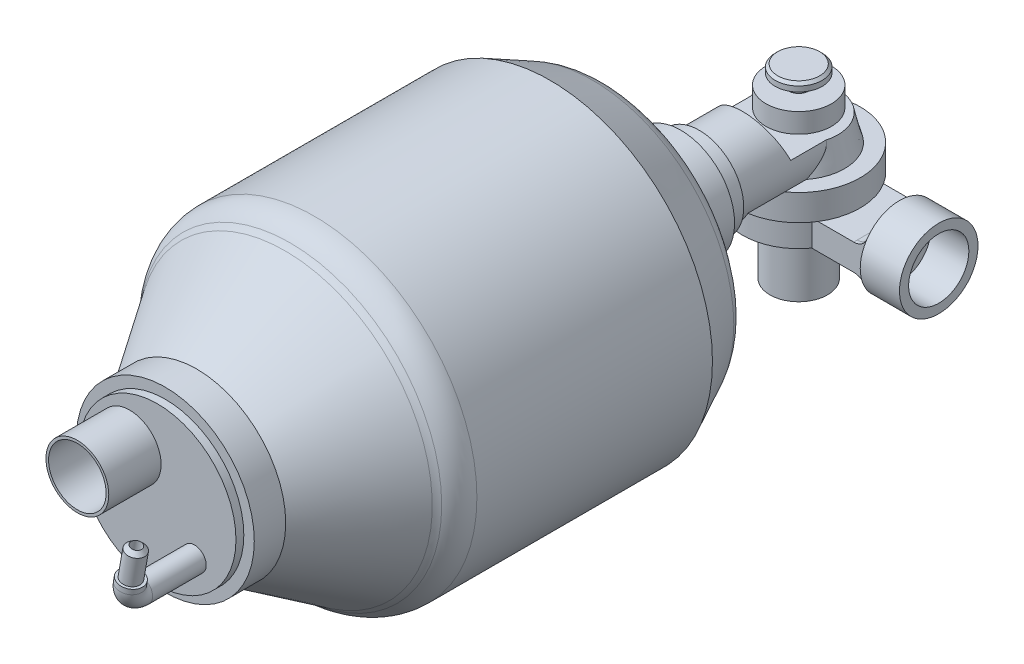
SolidWorks part; units mm, degrees
ref_plane "Front Plane" through (0, 0, 0) normal (0, 0, 1) x (1, 0, 0)
ref_plane "Top Plane" through (0, 0, 0) normal (0, 1, 0) x (1, 0, 0)
ref_plane "Right Plane" through (0, 0, 0) normal (1, 0, 0) x (0, 0, -1)
sketch "Sketch1" plane through (0, 0, 0) normal (1, 0, 0) x (0, 0, -1)
  line L5 (-92.5, 0) -> (92.5, 0)
  line L6 (92.5, 0) -> (92.5, 20.5)
  line L7 (-47.5, 62.05) -> (42.5, 62.05)
  line L8 (42.5, 62.05) -> (62.5, 52.05)
  line L9 (62.5, 52.05) -> (78.5, 20.5)
  line L10 (78.5, 20.5) -> (92.5, 20.5)
  line L11 (-47.5, 62.05) -> (-47.5, 57.05) construction
  line L12 (-47.5, 57.05) -> (-57.5, 57.05) construction
  line L13 (-92.5, 0) -> (-92.5, 34)
  line L14 (-92.5, 34) -> (-57.5, 57.05)
  arc A6 (-47.5, 62.05) -> (-57.5, 57.05) centre (-47.5, 49.55) ccw
  dimension "D4" = 50
  dimension "D11" = 5
  dimension "D1" = 185
  dimension "D2" = 20.5
  dimension "D3" = 90
  dimension "D5" = 20
  dimension "D6" = 10
  dimension "D7" = 62.05
  dimension "D8" = 14
  dimension "D9" = 10
  dimension "D10" = 34
revolve "Revolve1" add sketch "Sketch1" angle 360 about L5
fillet "Fillet1" radius 5 1 edges at (20.5, 0, -78.5)
fillet "Fillet2" radius 12.54 1 edges at (52.05, 0, -62.5)
fillet "Fillet5" radius 10 1 edges at (57.05, 0, 57.5)
sketch "Sketch2" plane through (0, 0, 92.5) normal (0, 0, 1) x (1, 0, 0)
  circle A0 centre (0, 0) radius 34
  circle A1 centre (0, 0) radius 34 construction
extrude "Boss-Extrude1" add sketch "Sketch2" along normal blind 12
sketch "Sketch3" plane through (0, 0, 104.5) normal (0, 0, 1) x (1, 0, 0)
  circle A0 centre (0, 0) radius 30
  dimension "D1" = 60
extrude "Boss-Extrude2" add sketch "Sketch3" along normal blind 3
sketch "Sketch4" plane through (0, 0, 107.5) normal (0, 0, 1) x (1, 0, 0)
  line L0 (-10.6066, 10.6066) -> (14.1421, -14.1421) construction
  line L1 (0, 0) -> (0, 16.2779) construction
  line L2 (14.1421, -14.1421) -> (16.6659, 0.1707) construction
  dimension "D4" = 55
  dimension "D1" = 45
  dimension "D2" = 15
  dimension "D3" = 20
sketch "Sketch5" plane through (0, 0, 107.5) normal (0, 0, 1) x (1, 0, 0)
  circle A0 centre (-10.6066, 10.6066) radius 12
  circle A1 centre (-10.6066, 10.6066) radius 11
  dimension "D1" = 24
  dimension "D2" = 22
extrude "Boss-Extrude3" add sketch "Sketch5" along normal blind 20
ref_plane "Plane2" through (16.1341, -2.8449, 0) normal (0.9848, -0.1736, 0) x (0.1736, 0.9848, 0)
sketch "Sketch10" plane through (16.1341, -2.8449, 0) normal (0.9848, -0.1736, 0) x (0.1736, 0.9848, 0)
  line L0 (-11.4715, 107.5) -> (-11.4715, 128)
  line L1 (-6.4715, 133) -> (-4.4715, 133)
  arc A0 (-11.4715, 128) -> (-6.4715, 133) centre (-6.4715, 128) cw
  dimension "D3" = 5
  dimension "D1" = 7
  dimension "D2" = 25.5
sketch "Sketch8" plane through (0, 0, 107.5) normal (0, 0, 1) x (1, 0, 0)
  circle A0 centre (14.1421, -14.1421) radius 4.5
  circle A2 centre (14.1421, -14.1421) radius 2.5
  dimension "D1" = 9
  dimension "D2" = 5
sweep "Sweep2" add profiles "Sketch8" path "Sketch10"
sketch "Sketch13" plane through (-0.7765, -4.4036, 0) normal (0.1736, 0.9848, 0) x (0.9848, -0.1736, 0)
  circle A0 centre (16.383, -133) radius 3.5
  circle A1 centre (16.383, -133) radius 2
  dimension "D1" = 7
  dimension "D2" = 4
extrude "Boss-Extrude5" add sketch "Sketch13" along normal blind 12
chamfer "Chamfer2" distance 1.5 angle 45 1 edges at (13.9946, 5.177, 133)
sketch "Sketch15" plane through (0, 0, -92.5) normal (0, 0, -1) x (-1, 0, 0)
  circle A0 centre (0, 0) radius 17
  dimension "D1" = 34
extrude "Boss-Extrude6" add sketch "Sketch15" along normal blind 7
sketch "Sketch16" plane through (0, 0, -99.5) normal (0, 0, -1) x (-1, 0, 0)
  circle A0 centre (0, 0) radius 15
  dimension "D1" = 30
extrude "Boss-Extrude7" add sketch "Sketch16" along normal blind 45 from surface starting at face at (-17, 0, -92.5)
ref_plane "Plane3" through (0, 4, 0) normal (0, 1, 0) x (1, 0, 0)
sketch "Sketch21" plane through (0, 0, -137.5) normal (0, 0, -1) x (-1, 0, 0)
  line L0 (0, 0) -> (0, 4) construction
  line L1 (0, 0) -> (0, -6) construction
  point P4 (0, 4)
  dimension "D1" = 4
  dimension "D2" = 6
sketch "Sketch24" plane through (0, 4, 0) normal (0, 1, 0) x (1, 0, 0)
  circle A0 centre (0, 137.5) radius 15
  dimension "D1" = 30
ref_plane "Plane4" through (0, -6, 0) normal (0, 1, 0) x (1, 0, 0)
sketch "Sketch25" plane through (0, -6, 0) normal (0, 1, 0) x (1, 0, 0)
  circle A0 centre (0, 137.5) radius 17.5
  dimension "D1" = 35
loft "Loft1" add profiles "Sketch25", "Sketch24" connector at (-3.5057, -6, -154.6453) connector at (-0.8854, 4, -152.4738)
sketch "Sketch26" plane through (0, 0, 0) normal (1, 0, 0) x (0, 0, -1)
  line L0 (137.5, 4) -> (120, 4)
  line L1 (68.255, 4) -> (-68.255, 4) construction
  line L2 (120, 4) -> (115.6324, 16)
  line L3 (115.6324, 16) -> (137.5, 16)
  line L4 (137.5, 16) -> (137.5, 4)
  line L5 (137.5, -6) -> (104.5, -6)
  line L6 (137.5, 0) -> (137.5, -6) construction
  line L7 (68.255, -6) -> (-68.255, -6) construction
  line L8 (104.5, -6) -> (100.8603, -16)
  line L9 (100.8603, -16) -> (137.5, -16)
  line L10 (137.5, -16) -> (137.5, -6)
  line L11 (99.5, -15) -> (99.5, 15) construction
  dimension "D1" = 17.5
  dimension "D2" = 70
  dimension "D3" = 12
  dimension "D4" = 70
  dimension "D5" = 5
  dimension "D6" = 10
extrude "Cut-Extrude1" cut sketch "Sketch26" against normal mid plane 40
sketch "Sketch27" plane through (0, -6, 0) normal (0, -1, 0) x (1, 0, 0)
  circle A0 centre (0, -137.5) radius 23.5
  dimension "D1" = 47
extrude "Boss-Extrude8" add sketch "Sketch27" along normal blind 10
sketch "Sketch28" plane through (0, -16, 0) normal (0, -1, 0) x (1, 0, 0)
  circle A0 centre (0, -137.5) radius 21.5
  dimension "D1" = 43
extrude "Boss-Extrude9" add sketch "Sketch28" along normal blind 10
sketch "Sketch29" plane through (0, 4, 0) normal (0, 1, 0) x (1, 0, 0)
  circle A0 centre (0, 137.5) radius 10
  dimension "D1" = 20
extrude "Boss-Extrude10" add sketch "Sketch29" along normal blind 9
ref_plane "Plane5" through (0, 5.5, 0) normal (0, 1, 0) x (1, 0, 0)
sketch "Sketch30" plane through (0, 5.5, 0) normal (0, 1, 0) x (1, 0, 0)
  circle A0 centre (0, 137.5) radius 12.5
  dimension "D1" = 25
extrude "Boss-Extrude11" add sketch "Sketch30" along normal up to surface (7.5 mm away) up to face at (0, 13, -127.5)
sketch "Sketch31" plane through (0, 13, 0) normal (0, 1, 0) x (1, 0, 0)
  circle A0 centre (0, 137.5) radius 4
  dimension "D1" = 8
extrude "Boss-Extrude12" add sketch "Sketch31" along normal blind 1.5
sketch "Sketch32" plane through (0, 14.5, 0) normal (0, 1, 0) x (1, 0, 0)
  circle A0 centre (0, 137.5) radius 3
  dimension "D1" = 6
extrude "Boss-Extrude13" add sketch "Sketch32" along normal blind 1.5 contours A0
sketch "Sketch33" plane through (0, 16, 0) normal (0, 1, 0) x (1, 0, 0)
  circle A0 centre (0, 137.5) radius 3.5
  dimension "D1" = 7
extrude "Boss-Extrude14" add sketch "Sketch33" along normal blind 1
sketch "Sketch37" plane through (0, 17, 0) normal (0, 1, 0) x (1, 0, 0)
  circle A0 centre (0, 137.5) radius 9
  dimension "D1" = 18
extrude "Boss-Extrude15" add sketch "Sketch37" along normal blind 3
chamfer "Chamfer3" distance 1 angle 45 1 edges at (0, 20, -128.5)
sketch "Sketch38" plane through (0, -26, 0) normal (0, -1, 0) x (1, 0, 0)
  circle A0 centre (0, -137.5) radius 11
  dimension "D1" = 22
extrude "Boss-Extrude16" add sketch "Sketch38" along normal blind 25
ref_plane "Plane6" through (0, -31.5, 0) normal (0, -1, 0) x (-1, 0, 0)
sketch "Sketch39" plane through (0, -31.5, 0) normal (0, -1, 0) x (-1, 0, 0)
  circle A0 centre (0, 137.5) radius 12
  dimension "D1" = 24
extrude "Boss-Extrude17" add sketch "Sketch39" along normal mid plane 1
sketch "Sketch41" plane through (0, -51, 0) normal (0, -1, 0) x (1, 0, 0)
  circle A0 centre (0, -137.5) radius 8
  dimension "D1" = 16
extrude "Cut-Extrude2" cut sketch "Sketch41" against normal up to surface (25 mm away) up to face at (0, -26, -148.5)
ref_axis "Axis1" through (0, -64.7723, -137.5) along (0, 1, 0)
sketch "Sketch42" plane through (0, 0, 0) normal (1, 0, 0) x (0, 0, -1)
  line L0 (116, -26) -> (159, -26) construction
  line L1 (125, -26) -> (150, -26)
  line L2 (125, -26) -> (125, -16)
  line L3 (125, -16) -> (150, -16)
  line L4 (150, -26) -> (150, -16)
  line L5 (116, -16) -> (159, -16) construction
  line L6 (137.5, -64.7723) -> (137.5, 35.1869) construction
  point P10 (137.5, -16)
  dimension "D1" = 25
extrude "Boss-Extrude18" add sketch "Sketch42" along normal blind 38.5
sketch "Sketch43" plane through (38.5, 0, 0) normal (1, 0, 0) x (0, 0, -1)
  line L0 (137.5, -16) -> (137.5, -26) construction
  line L1 (150, -16) -> (125, -16) construction
  line L2 (125, -26) -> (150, -26) construction
  circle A0 centre (137.5, -21) radius 15
  dimension "D1" = 30
extrude "Boss-Extrude19" add sketch "Sketch43" along normal blind 15
sketch "Sketch44" plane through (53.5, 0, 0) normal (1, 0, 0) x (0, 0, -1)
  circle A0 centre (137.5, -21) radius 11.5
  dimension "D1" = 23
extrude "Cut-Extrude3" cut sketch "Sketch44" against normal blind 14.5
fillet "Fillet8" radius 5 2 edges at (38.5, -26, -137.5) (38.5, -16, -137.5)
sketch "Sketch45" plane through (39, 0, 0) normal (1, 0, 0) x (0, 0, -1)
  line L0 (137.5, -64.7723) -> (137.5, 35.1869) construction
  line L1 (126, -25) -> (149, -25)
  line L2 (126, -25) -> (126, -17)
  line L3 (126, -17) -> (149, -17)
  line L4 (149, -25) -> (149, -17)
  line L6 (125, -21) -> (126, -21) construction
  line L7 (125, -16) -> (125, -26) construction
  line L8 (126.3197, -16) -> (148.6803, -16) construction
  point P4 (137.5, -17)
  dimension "D1" = 1
  dimension "D2" = 1
extrude "Cut-Extrude4" cut sketch "Sketch45" against normal blind 30
sketch "Sketch46" plane through (0, 0, 0) normal (1, 0, 0) x (0, 0, -1)
  line L0 (137.5, -64.7723) -> (137.5, 35.1869) construction
  line L1 (116, -26) -> (159, -26) construction
  circle A0 centre (137.5, -23) radius 3
  circle A1 centre (137.5, -23) radius 1.75
  dimension "D1" = 6
  dimension "D2" = 3.5
extrude "Boss-Extrude20" add sketch "Sketch46" against normal blind 35.5
